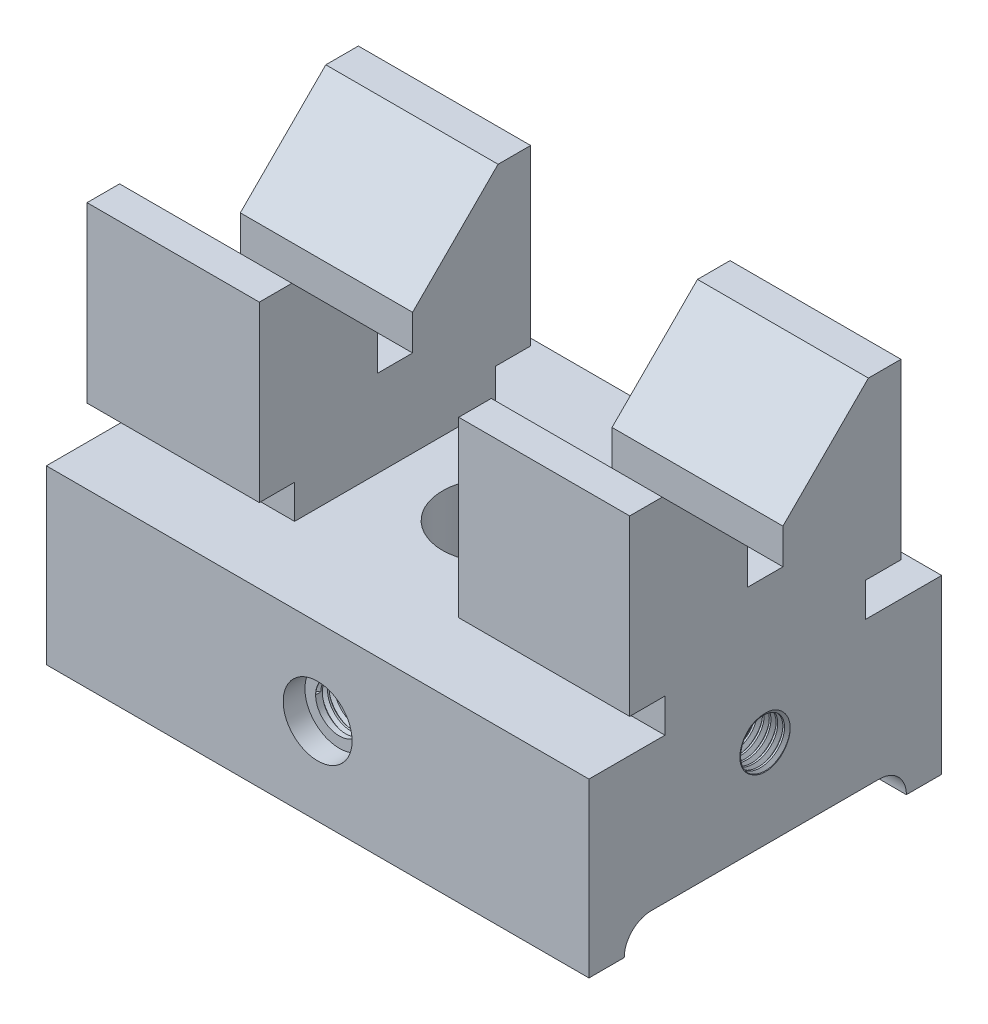
SolidWorks part; units mm, degrees
ref_plane "Front Plane" through (0, 0, 0) normal (0, 0, 1) x (1, 0, 0)
ref_plane "Top Plane" through (0, 0, 0) normal (0, 1, 0) x (1, 0, 0)
ref_plane "Right Plane" through (0, 0, 0) normal (1, 0, 0) x (0, 0, -1)
sketch "Sketch1" plane through (0, 0, 0) normal (1, 0, 0) x (0, 0, -1)
  line L1 (-32.5, 35) -> (32.5, 35)
  line L2 (-32.5, 35) -> (-32.5, -35)
  line L3 (-32.5, -35) -> (32.5, -35)
  line L4 (32.5, 35) -> (32.5, -35)
  line L5 (-32.5, 35) -> (32.5, -35) construction
  line L6 (-32.5, -35) -> (32.5, 35) construction
  point P0 (0, 0)
  dimension "D1" = 65
  dimension "D2" = 70
extrude "Boss-Extrude1" add sketch "Sketch1" along normal mid plane 100
sketch "Sketch2" plane through (50, 0, 0) normal (1, 0, 0) x (0, 0, -1)
  line L0 (0, 53.4813) -> (0, -46.6435) construction
  line L1 (-32.5, -3.25) -> (-18.5, -3.25)
  line L2 (-32.5, 35) -> (-32.5, -35) construction
  line L3 (-18.5, -3.25) -> (-18.5, 3)
  line L4 (-18.5, 3) -> (-25, 3)
  line L5 (-25, 3) -> (-25, 18.6462)
  line L6 (-25, 18.6462) -> (-25, 35)
  line L7 (32.5, 35) -> (-32.5, 35) construction
  line L8 (-3.25, 19.25) -> (-19, 35)
  line L9 (-3.25, 19.25) -> (-3.25, 12.75)
  line L10 (3.25, 19.25) -> (19, 35)
  line L11 (25, 18.6462) -> (25, 35)
  line L12 (25, 3) -> (25, 18.6462)
  line L13 (18.5, 3) -> (25, 3)
  line L14 (18.5, -3.25) -> (18.5, 3)
  line L15 (32.5, -3.25) -> (18.5, -3.25)
  line L16 (-3.25, 12.75) -> (3.25, 12.75)
  line L17 (3.25, 12.75) -> (3.25, 19.25)
  line L18 (-32.5, -35) -> (32.5, -35) construction
  line L19 (32.5, -35) -> (32.5, 35) construction
  line L20 (-26, -35) -> (26, -35)
  line L21 (-26, -35) -> (-26, -30)
  line L22 (-26, -30) -> (26, -30)
  line L23 (26, -35) -> (26, -30)
  point P16 (0, 14.2658)
  line M1 (32.5, -35) -> (32.5, 35)
  line M2 (32.5, 35) -> (-32.5, 35)
  line M3 (-32.5, 35) -> (-32.5, -35)
  line M4 (-32.5, -35) -> (32.5, -35)
  dimension "D1" = 14
  dimension "D2" = 50
  dimension "D3" = 38
  dimension "D4" = 38
  dimension "D5" = 47.75
  dimension "D6" = 31.75
  dimension "D7" = 90
  dimension "D8" = 6.5
  dimension "D9" = 19
  dimension "D10" = 5
  dimension "D11" = 6.5
  dimension "D12" = 6.5
extrude "Cut-Extrude1" cut sketch "Sketch2" against normal through all contours L5 L6 L1 L3 L4 M2 M3 | L15 L11 L12 L13 L14 M1 M2 | L0 L16 L17 L10 M2 | L0 L8 L9 L16 M2 | L22 L0 L20 L23 | L0 L22 L21 M4 region at (50, 27.5863, -5.968) region at (50, 27.5863, 5.968) region at (50, -32.5, -13) region at (50, -32.5, 13) region at (50, 13.8903, -27.8817) region at (50, 13.8903, 27.8817)
fillet "Fillet1" radius 5 2 edges at (0, -30, 26) (0, -30, -26)
sketch "Sketch4" plane through (-50, 0, 0) normal (-1, 0, 0) x (0, 0, 1)
  line L0 (-18.5, -3.25) -> (18.5, -3.25)
  line L20 (-32.5, -35) -> (-26, -35)
  line L21 (-21, -30) -> (21, -30)
  line L22 (26, -35) -> (32.5, -35)
  line L23 (32.5, -35) -> (32.5, -3.25)
  line L24 (32.5, -3.25) -> (18.5, -3.25)
  line L25 (18.5, -3.25) -> (18.5, 3)
  line L26 (18.5, 3) -> (25, 3)
  line L27 (25, 3) -> (25, 35)
  line L28 (25, 35) -> (19, 35)
  line L29 (19, 35) -> (3.25, 19.25)
  line L30 (3.25, 19.25) -> (3.25, 12.75)
  line L31 (3.25, 12.75) -> (-3.25, 12.75)
  line L32 (-3.25, 12.75) -> (-3.25, 19.25)
  line L33 (-3.25, 19.25) -> (-19, 35)
  line L34 (-19, 35) -> (-25, 35)
  line L35 (-25, 35) -> (-25, 3)
  line L36 (-25, 3) -> (-18.5, 3)
  line L37 (-18.5, 3) -> (-18.5, -3.25)
  line L38 (-18.5, -3.25) -> (-32.5, -3.25)
  line L39 (-32.5, -3.25) -> (-32.5, -35)
  line L40 (-32.5, -35) -> (-26, -35)
  line L41 (-21, -30) -> (21, -30)
  line L42 (26, -35) -> (32.5, -35)
  line L43 (32.5, -35) -> (32.5, -3.25)
  line L44 (32.5, -3.25) -> (18.5, -3.25)
  line L45 (18.5, -3.25) -> (18.5, 3)
  line L46 (18.5, 3) -> (25, 3)
  line L47 (25, 3) -> (25, 35)
  line L48 (25, 35) -> (19, 35)
  line L49 (19, 35) -> (3.25, 19.25)
  line L50 (3.25, 19.25) -> (3.25, 12.75)
  line L51 (3.25, 12.75) -> (-3.25, 12.75)
  line L52 (-3.25, 12.75) -> (-3.25, 19.25)
  line L53 (-3.25, 19.25) -> (-19, 35)
  line L54 (-19, 35) -> (-25, 35)
  line L55 (-25, 35) -> (-25, 3)
  line L56 (-25, 3) -> (-18.5, 3)
  line L57 (-18.5, 3) -> (-18.5, -3.25)
  line L58 (-18.5, -3.25) -> (-32.5, -3.25)
  line L59 (-32.5, -3.25) -> (-32.5, -35)
  arc A2 (-21, -30) -> (-26, -35) centre (-21, -35) ccw
  arc A3 (26, -35) -> (21, -30) centre (21, -35) ccw
  arc A4 (-21, -30) -> (-26, -35) centre (-21, -35) ccw
  arc A5 (26, -35) -> (21, -30) centre (21, -35) ccw
  line M30 (18.5, -3.25) -> (18.5, 3)
  line M31 (18.5, 3) -> (25, 3)
  line M32 (25, 3) -> (25, 35)
  line M33 (25, 35) -> (19, 35)
  line M34 (19, 35) -> (3.25, 19.25)
  line M35 (3.25, 19.25) -> (3.25, 12.75)
  line M36 (3.25, 12.75) -> (-3.25, 12.75)
  line M37 (-3.25, 12.75) -> (-3.25, 19.25)
  line M38 (-3.25, 19.25) -> (-19, 35)
  line M39 (-19, 35) -> (-25, 35)
  line M40 (-25, 35) -> (-25, 3)
  line M41 (-25, 3) -> (-18.5, 3)
  line M42 (-18.5, 3) -> (-18.5, -3.25)
  dimension "D1" = 0
extrude "Cut-Extrude2" cut sketch "Sketch4" against normal blind 36.75 from offset 31.75 contours L0 M42 M30 M31 M32 M33 M34 M35 M36 M37 M38 M39 M40 M41 region at (-50, -0.125, -17.8705) offset against normal yes
sketch "Sketch5" plane through (0, -3.25, 0) normal (0, 1, 0) x (1, 0, 0)
  circle A0 centre (0, 0) radius 9.5
  dimension "D1" = 19
extrude "Cut-Extrude3" cut sketch "Sketch5" against normal through all
hole_wizard "CBORE for M10 Hex Head Bolt1" positions "Sketch7" profile "Sketch8" counterbore size "M10" standard "ANSI Metric"
sketch "Sketch7" plane through (0, 0, 32.5) normal (0, 0, 1) x (1, 0, 0)
  line L0 (50, -35) -> (-50, -35) construction
  line L3 (50, -3.25) -> (50, -35) construction
  point P0 (0, -19)
  point P9 (50, -22.0835)
  point P14 (0, 0)
  dimension "D1" = 16
  dimension "D2" = 50
sketch "Sketch8" plane through (0, -19, 32.5) normal (1, 0, 0) x (0, -1, 0)
  line L0 (0, 0) -> (0, 22.6288)
  line L1 (0, 22.6288) -> (4.375, 20)
  line L2 (4.375, 20) -> (4.375, 4)
  line L3 (4.375, 4) -> (6.35, 4)
  line L4 (6.35, 4) -> (6.35, 0)
  line L5 (6.35, 0) -> (0, 0)
  line L10 (0, 22.6288) -> (-4.375, 20) construction
  line L11 (0, -6.35) -> (0, 107.95) construction
  dimension "Hole Dia." = 8.75
  dimension "Hole Depth" = 20
  dimension "C'Bore Dia." = 12.7
  dimension "C'Bore Depth" = 4
  dimension "Drill Angle" = 118
thread "Thread1" pitch 1.25 method cut profile "Thread Profile1" start angle 0, offset 0, length 10, pitch 1.25, diameter 8.75
ref_plane "Plane1" through (-4.375, -19, 28.5) normal (0, -1, 0) x (-1, 0, 0)
sketch "Thread Profile1" plane through (-4.375, -19, 28.5) normal (0, -1, 0) x (-1, 0, 0)
  line L0 (0, 0) -> (0, 1.25) construction
  line L1 (0, 0) -> (0.6766, 0.3906)
  line L2 (0.6766, 0.3906) -> (0.6766, 0.5469)
  line L3 (0.6766, 0.5469) -> (0, 0.9375)
  line L4 (0.6766, 0.4687) -> (0, 0.4687) construction
  line L11 (0, 0) -> (0, 0.9375)
  point P2 (0, 0)
  dimension "Pitch" = 1.25
  dimension "Profile_Angle" = 60
  dimension "Profile_Land" = 0.1562
  dimension "Profile_Height" = 0.6766
hole_wizard "Ø8.7 (8.7) Diameter Hole1" positions "Sketch15" profile "Sketch16" hole size "Ø8.7" standard "ANSI Metric"
sketch "Sketch15" plane through (50, 0, 0) normal (1, 0, 0) x (0, 0, -1)
  line L0 (-21, -30) -> (21, -30) construction
  line L1 (-32.5, -3.25) -> (-32.5, -35) construction
  point P1 (0, -14)
  dimension "D1" = 16
  dimension "D2" = 32.5
sketch "Sketch16" plane through (50, -14, 0) normal (0, 1, 0) x (0, 0, -1)
  line L0 (0, 0) -> (0, 18.6137)
  line L1 (0, 18.6137) -> (4.35, 16)
  line L2 (4.35, 16) -> (4.35, 0)
  line L5 (4.35, 0) -> (0, 0)
  line L10 (0, 18.6137) -> (-4.35, 16) construction
  line L11 (0, -6.35) -> (0, 107.95) construction
  dimension "Hole Dia." = 8.7
  dimension "Hole Depth" = 16
  dimension "Drill Angle" = 118
thread "Thread2" pitch 1.25 method cut profile "Thread Profile2" start angle 0, offset 2, length 16, pitch 1.25, diameter 8.7
ref_plane "Plane2" through (52, -14, 4.35) normal (0, -1, 0) x (0, 0, 1)
sketch "Thread Profile2" plane through (52, -14, 4.35) normal (0, -1, 0) x (0, 0, 1)
  line L0 (0, 0) -> (0, 1.25) construction
  line L1 (0, 0) -> (0.6766, 0.3906)
  line L2 (0.6766, 0.3906) -> (0.6766, 0.5469)
  line L3 (0.6766, 0.5469) -> (0, 0.9375)
  line L4 (0.6766, 0.4687) -> (0, 0.4687) construction
  line L11 (0, 0) -> (0, 0.9375)
  point P2 (0, 0)
  dimension "Pitch" = 1.25
  dimension "Profile_Angle" = 60
  dimension "Profile_Land" = 0.1562
  dimension "Profile_Height" = 0.6766
